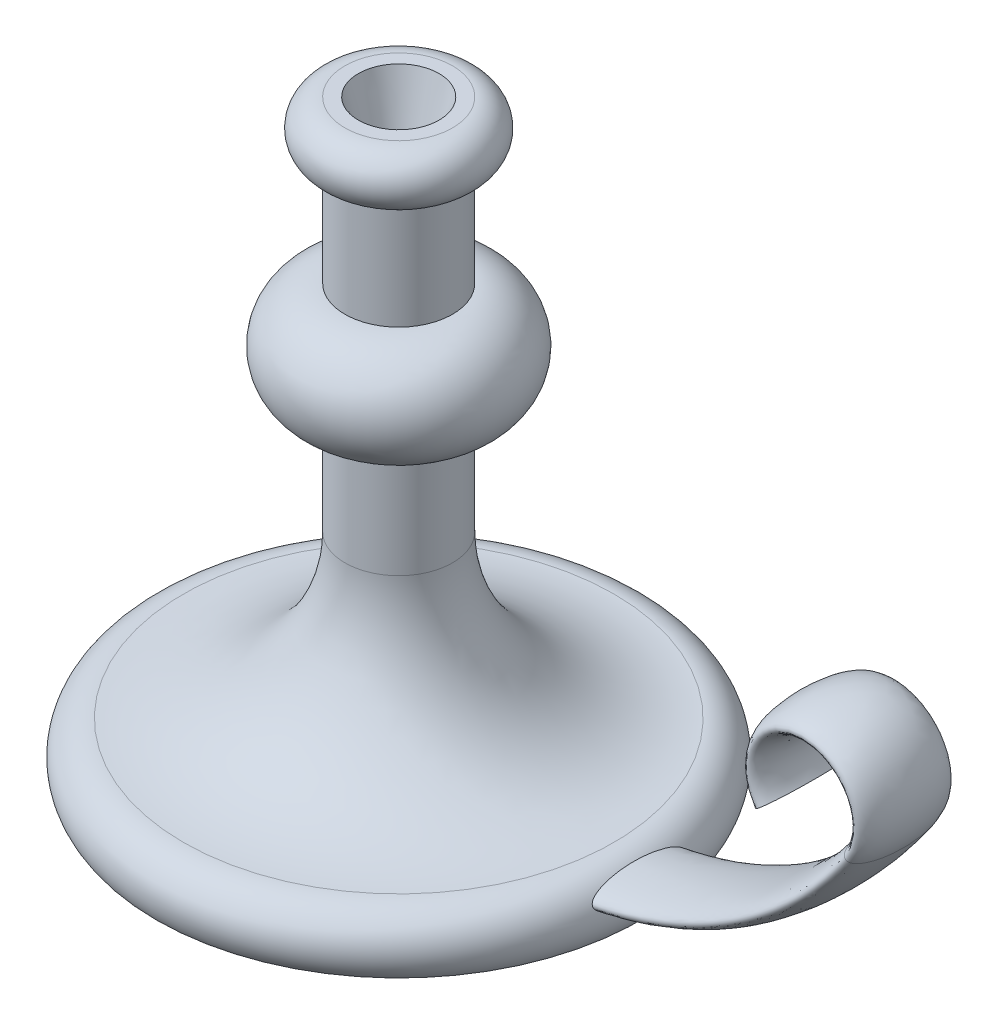
SolidWorks part; units mm, degrees
ref_plane "Front Plane" through (0, 0, 0) normal (0, 0, 1) x (1, 0, 0)
ref_plane "Top Plane" through (0, 0, 0) normal (0, 1, 0) x (1, 0, 0)
ref_plane "Right Plane" through (0, 0, 0) normal (1, 0, 0) x (0, 0, -1)
sketch "Sketch1" plane through (0, 0, 0) normal (0, 0, 1) x (1, 0, 0)
  line L0 (0, 0) -> (90, 0)
  line L1 (90, 0) -> (0, 0)
  line L2 (0, 0) -> (0, 220)
  line L3 (0, 220) -> (20, 220)
  line L4 (20, 200) -> (20, 160)
  line L5 (20, 120) -> (20, 80)
  arc A0 (20, 220) -> (20, 200) centre (20, 210) cw
  arc A1 (20, 160) -> (20, 120) centre (20, 140) cw
  arc A2 (20, 80) -> (80, 20) centre (80, 80) ccw
  arc A3 (80, 20) -> (90, 0) centre (80, 7.5) cw
  dimension "D5" = 20
  dimension "D7" = 60
  dimension "D4" = 10
  dimension "D8" = 12.5
  dimension "D1" = 220
  dimension "D2" = 90
  dimension "D3" = 20
  dimension "D6" = 40
  dimension "D9" = 80
revolve "Revolve2" add sketch "Sketch1" angle 360 about L2 region at (2.3866, 110, 0)
sketch "Sketch2" plane through (0, 0, 0) normal (0, 0, 1) x (1, 0, 0)
  line L0 (0, 10) -> (60, 10)
  line L1 (0, 200) -> (0, 160) construction
  line L2 (-90, 0) -> (90, 0) construction
  arc A0 (60, 10) -> (183.5921, 75) centre (60, 160) ccw
  arc A1 (183.5921, 75) -> (150.6342, 75) centre (167.1131, 86.3333) ccw
  dimension "D2" = 150
  dimension "D4" = 20
  dimension "D1" = 60
  dimension "D3" = 65
  dimension "D5" = 10
sketch "Sketch3" plane through (0, 0, 0) normal (1, 0, 0) x (0, 0, -1)
  ellipse E0 centre (0, 10) end of major axis (17.5, 10) minor radius 5
  dimension "D1" = 10
  dimension "D2" = 35
sweep "Sweep1" add profiles "Sketch3" path "Sketch2"
sketch "Sketch4" plane through (0, 220, 0) normal (0, 1, 0) x (1, 0, 0)
  circle A0 centre (0, 0) radius 15
  dimension "D1" = 30
extrude "Cut-Extrude1" cut sketch "Sketch4" against normal blind 25 draft 15
